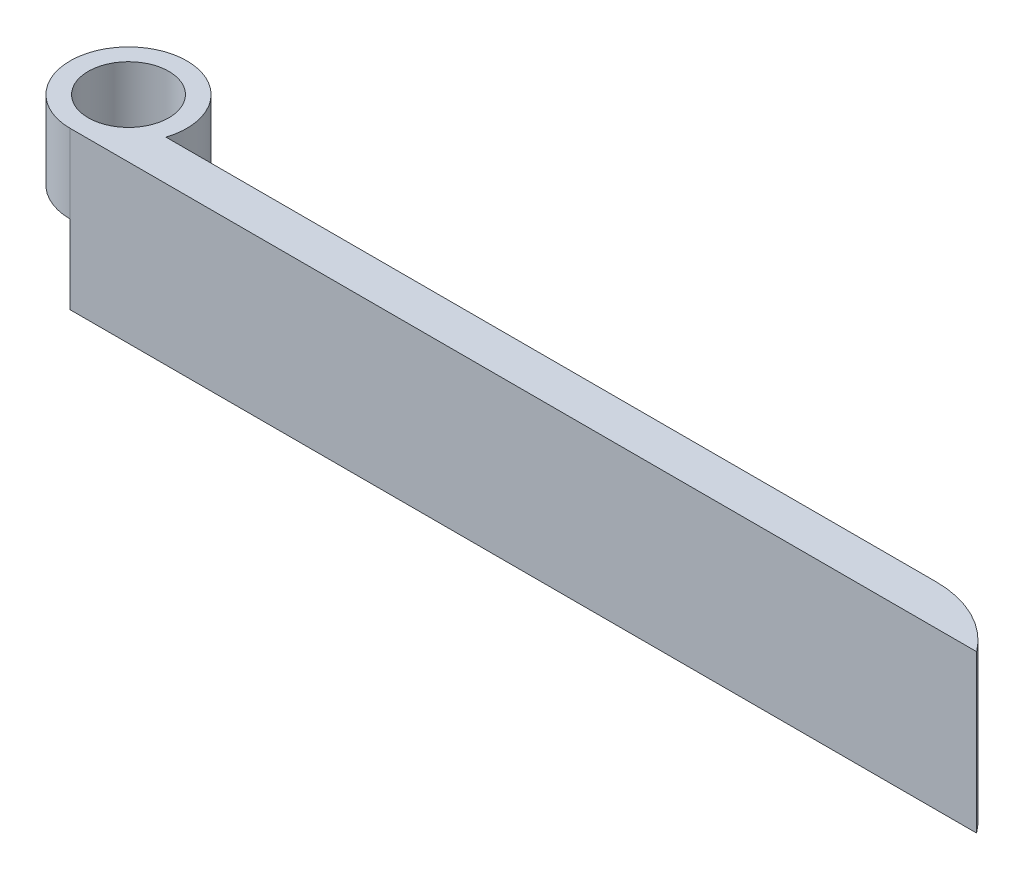
SolidWorks part; units mm, degrees
ref_plane "Alzado" through (0, 0, 0) normal (0, 0, 1) x (1, 0, 0)
ref_plane "Planta" through (0, 0, 0) normal (0, 1, 0) x (1, 0, 0)
ref_plane "Vista lateral" through (0, 0, 0) normal (1, 0, 0) x (0, 0, -1)
sketch "Croquis1" plane through (0, 0, 0) normal (0, 1, 0) x (1, 0, 0)
  line L0 (-14.1349, 0) -> (21.0104, 0) construction
  line L1 (0, 9.8879) -> (0, -9.2182) construction
  circle A0 centre (0, 0) radius 2.9
  circle A1 centre (0, 0) radius 2
  dimension "D1" = 5.8
  dimension "D2" = 4
extrude "Saliente-Extruir1" add sketch "Croquis1" along normal blind 3.9
sketch "Croquis3" plane through (0, 0, 0) normal (0, -1, 0) x (1, 0, 0)
  line L0 (0, 4.5432) -> (0, 2.9) construction
  line L1 (0, 2.9) -> (45, 2.9)
  line L2 (45, 2.9) -> (45, 0.9)
  line L3 (45, 0.9) -> (2.7568, 0.9)
  line L5 (0, 5.0665) -> (0, -5.1763) construction
  circle A0 centre (0, 0) radius 2.9
  dimension "D1" = 5.8
  dimension "D2" = 45
  dimension "D3" = 2
extrude "Saliente-Extruir2" add sketch "Croquis3" along normal blind 3.9 and the other way blind 3.9 contours L3 L2 L1 L5 region at (23.5049, 0, 1.908)
fillet "Redondeo1" radius 5 1 edges at (45, 0, 0.9)
